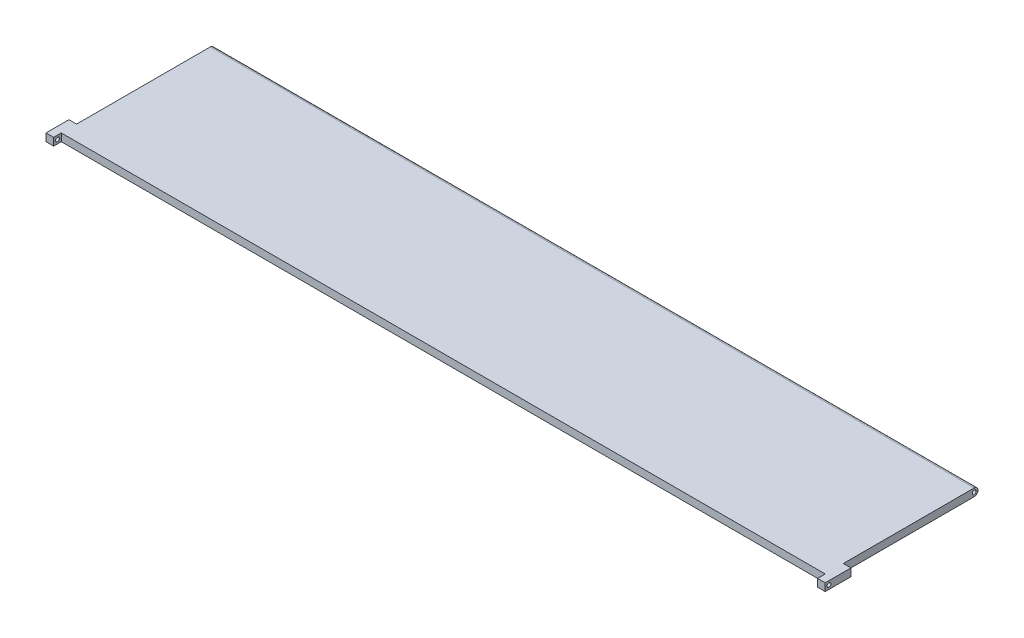
SolidWorks part; units mm, degrees
ref_plane "Front Plane" through (0, 0, 0) normal (0, 0, 1) x (1, 0, 0)
ref_plane "Top Plane" through (0, 0, 0) normal (0, 1, 0) x (1, 0, 0)
ref_plane "Right Plane" through (0, 0, 0) normal (1, 0, 0) x (0, 0, -1)
sketch "Sketch1" plane through (0, 0, 0) normal (0, 1, 0) x (1, 0, 0)
  line L1 (100, -20) -> (-100, -20)
  line L2 (100, -20) -> (100, 20)
  line L3 (100, 20) -> (-100, 20)
  line L4 (-100, -20) -> (-100, 20)
  line L5 (100, -20) -> (-100, 20) construction
  line L6 (100, 20) -> (-100, -20) construction
  point P0 (0, 0)
  dimension "D1" = 200
  dimension "D2" = 40
extrude "Boss-Extrude1" add sketch "Sketch1" along normal blind 2
sketch "Sketch2" plane through (100, 0, 0) normal (1, 0, 0) x (0, 0, -1)
  line L1 (-20, 2) -> (20, 2) construction
  line L2 (-15.2592, 2) -> (-22, 2)
  line L3 (-15.2592, 2) -> (-15.2592, 0)
  line L4 (-15.2592, 0) -> (-22, 0)
  line L5 (-22, 2) -> (-22, 0)
  line L6 (-20, 2) -> (-20, 0) construction
  circle A0 centre (-21, 1) radius 0.5
  point P9 (-20, 1)
  dimension "D1" = 1
  dimension "D2" = 1
  dimension "D3" = 1
extrude "Boss-Extrude2" add sketch "Sketch2" along normal blind 2
sketch "Sketch3" plane through (-100, 0, 0) normal (-1, 0, 0) x (0, 0, 1)
  line L1 (16, 0) -> (22, 0)
  line L2 (16, 0) -> (16, 2)
  line L3 (16, 2) -> (22, 2)
  line L4 (22, 0) -> (22, 2)
  line L5 (20, 2) -> (20, 0) construction
  circle A0 centre (21, 1) radius 0.5
  dimension "D1" = 1
  dimension "D2" = 1
  dimension "D3" = 1
extrude "Boss-Extrude3" add sketch "Sketch3" along normal blind 2
sketch "Sketch4" plane through (-100, 0, 0) normal (-1, 0, 0) x (0, 0, 1)
  line L0 (-20, 2) -> (-20, 0) construction
  circle A0 centre (-19, 1) radius 0.5
  dimension "D1" = 1
  dimension "D2" = 1
extrude "Cut-Extrude1" cut sketch "Sketch4" against normal through all
fillet "Fillet2" radius 1 2 edges at (0, 0, -20) (0, 2, -20)
